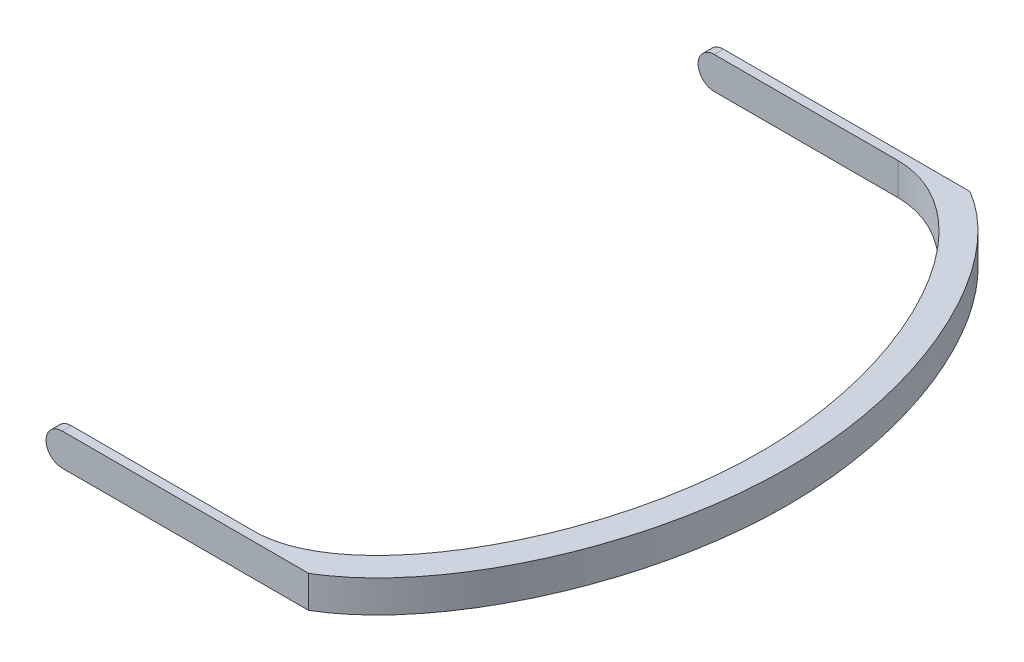
SolidWorks part; units mm, degrees
ref_plane "Front Plane" through (0, 0, 0) normal (0, 0, 1) x (1, 0, 0)
ref_plane "Top Plane" through (0, 0, 0) normal (0, 1, 0) x (1, 0, 0)
ref_plane "Right Plane" through (0, 0, 0) normal (1, 0, 0) x (0, 0, -1)
sketch "Sketch1" plane through (0, 0, 0) normal (0, 0, 1) x (1, 0, 0)
  line L0 (0, 8.89) -> (242.6115, 8.89)
  line L1 (242.6115, 8.89) -> (242.6115, -8.89)
  line L2 (242.6115, -8.89) -> (0, -8.89)
  circle A0 centre (0, 0) radius 3.81
  arc A1 (0, 8.89) -> (0, -8.89) centre (0, 0) ccw
  circle A3 centre (0, 0) radius 8.89 construction
  point P7 (8.89, 0)
  dimension "D1" = 7.62
  dimension "D3" = 242.6115
  dimension "D2" = 5.08
extrude "Boss-Extrude1" add sketch "Sketch1" along normal blind 182.88 and the other way blind 182.88 contours L0 L1 L2 A1
extrude "Cut-Extrude1" cut sketch "Sketch1<5>" against normal blind 177.8 and the other way blind 177.8 flip side to cut
sketch "Sketch1<5>" plane through (0, 0, 0) normal (0, 0, 1) x (1, 0, 0) same geometry as "Sketch1"
sketch "Sketch3" plane through (0, 0, 0) normal (0, 1, 0) x (1, 0, 0)
  line L1 (-101.6, 177.8) -> (101.6, 177.8)
  line L2 (-101.6, 177.8) -> (-101.6, -177.8)
  line L3 (-101.6, -177.8) -> (101.6, -177.8)
  line L4 (101.6, 177.8) -> (101.6, -177.8) construction
  line L5 (-101.6, 177.8) -> (101.6, -177.8) construction
  line L6 (-101.6, -177.8) -> (101.6, 177.8) construction
  line L7 (-9.779, 0) -> (9.779, 0) construction
  spline S0 degree 3 poles (101.6, 177.8) (152.4, 177.8) (254, 0) (152.4, -177.8) (101.6, -177.8) knots 0 0 0 0 0.5 1 1 1 1
  point P0 (0, 0)
  dimension "D3" = 152.4
  dimension "D4" = 152.4
  dimension "D1" = 355.6
  dimension "D2" = 203.2
extrude "Cut-Extrude2" cut sketch "Sketch3" against normal through all and the other way through all contours L1 S0 L3 L2
sketch "Sketch6" plane through (0, 8.89, 0) normal (0, 1, 0) x (1, 0, 0)
  line L1 (101.6, 193.04) -> (365.2136, 193.04)
  line L3 (101.6, -193.04) -> (365.2136, -193.04)
  line L4 (365.2136, 193.04) -> (365.2136, -193.04)
  spline S2 degree 3 poles (1199.8586, -2560.9322) (-231.3293, -137.9285) (-12.3426, 218.6255) (118.4331, 190.8036) (122.4836, 189.5111) (130.341, 186.2372) (134.1493, 184.2563) (141.5245, 179.7102) (145.0922, 177.1449) (152, 171.5035) (155.3403, 168.4272) (161.8025, 161.8181) (164.9244, 158.2851) (173.9638, 147.0681) (179.5576, 138.7664) (189.8064, 120.831) (194.46, 111.1964) (202.6844, 90.8989) (206.2547, 80.2359) (212.1337, 58.1896) (214.4423, 46.8062) (217.5954, 23.6306) (218.44, 11.8382) (218.44, -11.8382) (217.5954, -23.6306) (214.4423, -46.8062) (212.1337, -58.1896) (206.2547, -80.2359) (202.6844, -90.8989) (194.46, -111.1964) (189.8064, -120.831) (179.5576, -138.7664) (173.9638, -147.0681) (164.9244, -158.2851) (161.8025, -161.8181) (155.3403, -168.4272) (152, -171.5035) (145.0922, -177.1449) (141.5245, -179.7102) (134.1493, -184.2563) (130.341, -186.2372) (122.4836, -189.5111) (118.4331, -190.8036) (-12.3429, -218.6255) (-231.3305, 137.9305) (1199.8704, 2560.9523) knots -0.922441 -0.922441 -0.922441 -0.922441 0.03125 0.03125 0.0625 0.0625 0.09375 0.09375 0.125 0.125 0.15625 0.15625 0.1875 0.1875 0.25 0.25 0.3125 0.3125 0.375 0.375 0.4375 0.4375 0.5 0.5 0.5625 0.5625 0.625 0.625 0.6875 0.6875 0.75 0.75 0.8125 0.8125 0.84375 0.84375 0.875 0.875 0.90625 0.90625 0.9375 0.9375 0.96875 0.96875 1.922444 1.922444 1.922444 1.922444 only from (101.6, 193.04) to (101.6, -193.04)
  spline S3 degree 3 poles (101.6, 193.04) (105.8862, 193.04) (110.1346, 192.569) (118.4331, 190.8036) (122.4836, 189.5111) (130.341, 186.2372) (134.1493, 184.2563) (141.5245, 179.7102) (145.0922, 177.1449) (152, 171.5035) (155.3403, 168.4272) (161.8025, 161.8181) (164.9244, 158.2851) (173.9638, 147.0681) (179.5576, 138.7664) (189.8064, 120.831) (194.46, 111.1964) (202.6844, 90.8989) (206.2547, 80.2359) (212.1337, 58.1896) (214.4423, 46.8062) (217.5954, 23.6306) (218.44, 11.8382) (218.44, -11.8382) (217.5954, -23.6306) (214.4423, -46.8062) (212.1337, -58.1896) (206.2547, -80.2359) (202.6844, -90.8989) (194.46, -111.1964) (189.8064, -120.831) (179.5576, -138.7664) (173.9638, -147.0681) (164.9244, -158.2851) (161.8025, -161.8181) (155.3403, -168.4272) (152, -171.5035) (145.0922, -177.1449) (141.5245, -179.7102) (134.1493, -184.2563) (130.341, -186.2372) (122.4836, -189.5111) (118.4331, -190.8036) (110.1346, -192.569) (105.8862, -193.04) (101.6, -193.04) knots 0 0 0 0 0.03125 0.03125 0.0625 0.0625 0.09375 0.09375 0.125 0.125 0.15625 0.15625 0.1875 0.1875 0.25 0.25 0.3125 0.3125 0.375 0.375 0.4375 0.4375 0.5 0.5 0.5625 0.5625 0.625 0.625 0.6875 0.6875 0.75 0.75 0.8125 0.8125 0.84375 0.84375 0.875 0.875 0.90625 0.90625 0.9375 0.9375 0.96875 0.96875 1 1 1 1
  dimension "D1" = 15.24
extrude "Cut-Extrude3" cut sketch "Sketch6" against normal up to next contours L1 L4 L3 S3
